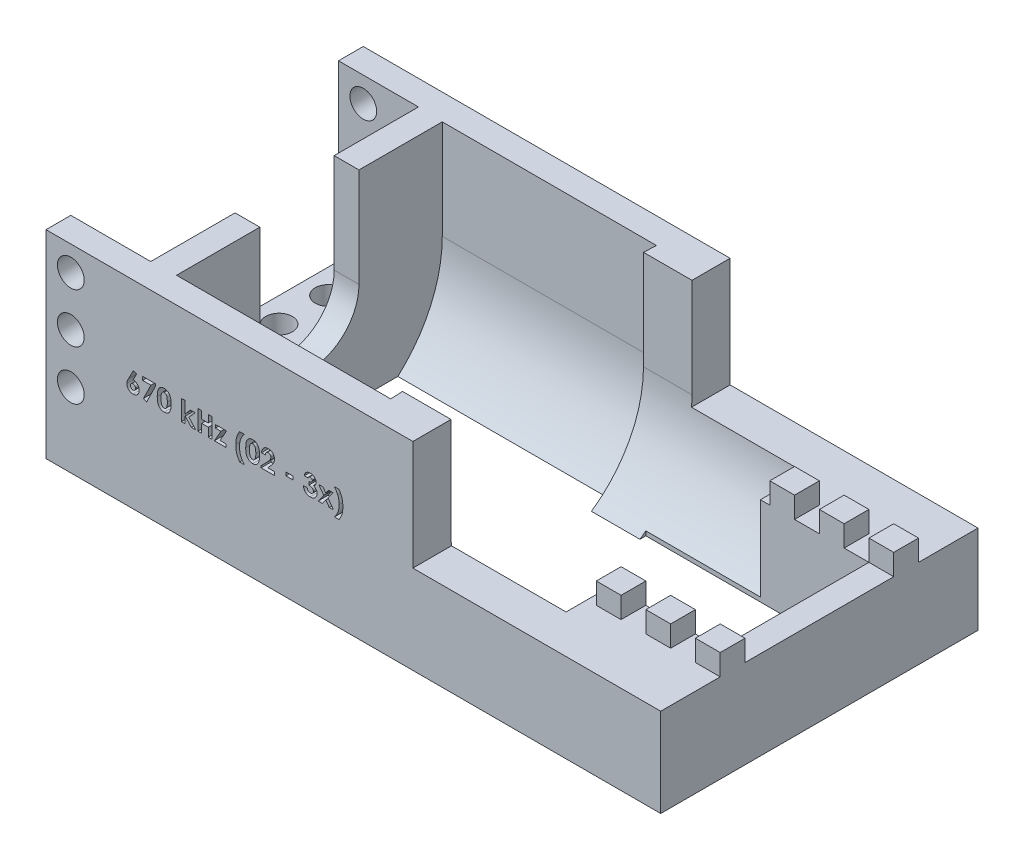
SolidWorks part; units mm, degrees
ref_plane "Front Plane" through (0, 0, 0) normal (0, 0, 1) x (1, 0, 0)
ref_plane "Top Plane" through (0, 0, 0) normal (0, 1, 0) x (1, 0, 0)
ref_plane "Right Plane" through (0, 0, 0) normal (1, 0, 0) x (0, 0, -1)
sketch "Sketch1" plane through (0, 0, 0) normal (0, 0, 1) x (1, 0, 0)
  line L1 (-76.2, -50.8) -> (81.28, -50.8)
  line L2 (-76.2, -50.8) -> (-76.2, 0)
  line L3 (-76.2, 0) -> (81.28, 0)
  line L4 (81.28, -50.8) -> (81.28, 0)
  line L5 (-76.2, -50.8) -> (81.28, 0) construction
  line L6 (-76.2, 0) -> (81.28, -50.8) construction
  point P0 (0, 0)
  dimension "D1" = 157.48
  dimension "D2" = 50.8
  dimension "D3" = 76.2
extrude "Boss-Extrude1" add sketch "Sketch1" along normal mid plane 81.28
sketch "Sketch2" plane through (0, 0, 0) normal (0, 0, 1) x (1, 0, 0)
  line L1 (-49.3609, 8.636) -> (-49.3609, -12.7)
  line L3 (81.28, 0) -> (-76.2, 0) construction
  line L4 (5.5031, 8.636) -> (5.3587, 5.4643)
  line L5 (3.9535, -25.4) -> (5.5031, 8.636) construction
  line L6 (-76.2, -25.4) -> (19.6294, -25.4)
  line L7 (19.6294, -25.4) -> (72.5335, -25.4)
  line L8 (-607.3619, -25.4) -> (19.6294, -25.4) construction
  line L9 (-49.3609, 8.636) -> (5.5031, 8.636)
  line L11 (5.3587, 5.4643) -> (47.1335, 5.4643)
  line L12 (47.1335, 5.4643) -> (47.1335, -15.494)
  line L13 (47.1335, -15.494) -> (72.5335, -15.494)
  line L14 (-49.3609, -12.7) -> (-76.2, -12.7)
  line L15 (-76.2, -12.7) -> (-76.2, -25.4)
  line L16 (81.28, 0) -> (-76.2, 0) construction
  line L17 (-76.2, 0) -> (-76.2, -50.8) construction
  line L20 (72.5335, -15.494) -> (72.5335, -25.4)
  line L21 (-76.2, 0) -> (-76.2, -50.8) construction
  point P23 (3.9535, -25.4)
  dimension "D1" = 25.4
  dimension "D2" = 54.864
  dimension "D3" = 34.036
  dimension "D4" = 68.58
  dimension "D5" = 9.906
  dimension "D6" = 3.175
  dimension "D7" = 26.8391
  dimension "D8" = 25.4
  dimension "D9" = 12.7
revolve "Cut-Revolve1" cut sketch "Sketch2" angle 360 about L8
sketch "Sketch37" plane through (81.28, 0, 0) normal (1, 0, 0) x (0, 0, -1)
  line L0 (40.64, -50.8) -> (40.64, 0) construction
  line L1 (-40.64, 0) -> (40.64, 0)
  line L2 (-40.64, 0) -> (-40.64, -25.4)
  line L3 (-40.64, -25.4) -> (40.64, -25.4)
  line L4 (40.64, 0) -> (40.64, -25.4)
  point P7 (0, -25.4)
  point P11 (0, 0)
  dimension "D1" = 25.4
extrude "Cut-Extrude32" cut sketch "Sketch37" against normal through all
sketch "Sketch39" plane through (0, -25.4, 0) normal (0, 1, 0) x (1, 0, 0)
  line L20 (-49.3609, -12.7) -> (-76.2, -12.7)
  line L21 (-49.3609, -12.7) -> (-76.2, -12.7)
  line L22 (-76.2, 40.64) -> (-76.2, 12.7)
  line L23 (-76.2, 40.64) -> (-76.2, 12.7)
  line L24 (-76.2, 12.7) -> (-49.3609, 12.7)
  line L25 (-76.2, -12.7) -> (-76.2, -40.64)
  line L26 (-76.2, -40.64) -> (81.28, -40.64)
  line L27 (81.28, -40.64) -> (81.28, 40.64)
  line L28 (81.28, 40.64) -> (-76.2, 40.64)
  line L29 (-76.2, 12.7) -> (-49.3609, 12.7)
  line L30 (-49.3609, 12.7) -> (-49.3609, 34.036)
  line L31 (-49.3609, 12.7) -> (-49.3609, 34.036)
  line L32 (-49.3609, 34.036) -> (5.5031, 34.036)
  line L33 (-49.3609, 34.036) -> (5.5031, 34.036)
  line L34 (5.5031, 34.036) -> (5.3587, 30.8643)
  line L35 (5.5031, 34.036) -> (5.3587, 30.8643)
  line L36 (5.3587, 30.8643) -> (47.1335, 30.8643)
  line L37 (5.3587, 30.8643) -> (47.1335, 30.8643)
  line L38 (47.1335, 30.8643) -> (47.1335, 9.906)
  line L39 (47.1335, 30.8643) -> (47.1335, 9.906)
  line L40 (47.1335, 9.906) -> (72.5335, 9.906)
  line L41 (47.1335, 9.906) -> (72.5335, 9.906)
  line L42 (72.5335, 9.906) -> (72.5335, -9.906)
  line L43 (72.5335, 9.906) -> (72.5335, -9.906)
  line L44 (72.5335, -9.906) -> (47.1335, -9.906)
  line L45 (72.5335, -9.906) -> (47.1335, -9.906)
  line L46 (47.1335, -9.906) -> (47.1335, -30.8643)
  line L47 (47.1335, -9.906) -> (47.1335, -30.8643)
  line L48 (47.1335, -30.8643) -> (5.3587, -30.8643)
  line L49 (-76.2, -12.7) -> (-76.2, -40.64)
  line L50 (-76.2, -40.64) -> (81.28, -40.64)
  line L51 (81.28, -40.64) -> (81.28, 40.64)
  line L52 (81.28, 40.64) -> (-76.2, 40.64)
  line L53 (47.1335, -30.8643) -> (5.3587, -30.8643)
  line L54 (5.3587, -30.8643) -> (5.5031, -34.036)
  line L55 (5.3587, -30.8643) -> (5.5031, -34.036)
  line L56 (5.5031, -34.036) -> (-49.3609, -34.036)
  line L57 (5.5031, -34.036) -> (-49.3609, -34.036)
  line L58 (-49.3609, -34.036) -> (-49.3609, -12.7)
  line L59 (-49.3609, -34.036) -> (-49.3609, -12.7)
  dimension "D1" = 0
extrude "Boss-Extrude5" add sketch "Sketch39" along normal blind 25.4
ref_axis "Axis1" through (72.5335, -25.4, 0) along (-1, 0, 0)
ref_plane "Plane_Mid" through (0, -25.4, 0) normal (0, 1, 0) x (1, 0, 0)
ref_plane "Plane3" through (0, -28.0987, 0) normal (0, 1, 0) x (1, 0, 0)
sketch "Sketch45" plane through (0, 0, 0) normal (0, 0, 1) x (1, 0, 0)
  line L1 (27.94, -28.0987) -> (-27.94, -28.0988) construction
  line L2 (81.28, 0) -> (17.78, 0)
  line L4 (81.28, 0) -> (81.28, -28.0987)
  line L5 (81.28, -28.0987) -> (17.78, -28.0987)
  line L8 (17.78, 0) -> (17.78, -28.0987)
  dimension "D1" = 63.5
extrude "Cut-Extrude54" cut sketch "Sketch45" against normal through all both and the other way through all
ref_plane "Plane1" through (-74.7609, 0, 0) normal (1, 0, 0) x (0, 0, -1)
sketch "Sketch97" plane through (0, 0, 0) normal (0, 1, 0) x (1, 0, 0)
  line L0 (-76.2, -40.64) -> (17.78, -40.64) construction
  line L1 (-76.2, 40.64) -> (-55.7109, 40.64)
  line L2 (-76.2, 40.64) -> (-76.2, -40.64)
  line L3 (-76.2, -40.64) -> (-55.7109, -40.64)
  line L4 (-55.7109, 40.64) -> (-55.7109, -40.64)
  line L5 (-49.3609, 12.7) -> (-49.3609, 34.036) construction
  dimension "D1" = 6.35
extrude "Cut-Extrude72" cut sketch "Sketch97" against normal offset from surface (44.45 mm away) 6.35 up to face at (2.54, -50.8, 0)
sketch "Sketch98" plane through (0, -44.45, 0) normal (0, 1, 0) x (1, 0, 0)
  line L0 (-76.2, -40.64) -> (-76.2, 40.64) construction
  circle A0 centre (-69.85, 25.4) radius 3.429
  circle A4 centre (-69.85, 12.7) radius 3.429
  circle A5 centre (-69.85, 0) radius 3.429
  circle A6 centre (-57.15, 25.4) radius 3.429 [skipped]
  circle A7 centre (-57.15, 12.7) radius 3.429 [skipped]
  circle A8 centre (-57.15, 0) radius 3.429 [skipped]
  circle A9 centre (-69.85, -12.7) radius 3.429
  circle A11 centre (-69.85, -25.4) radius 3.429
  circle A13 centre (-57.15, -12.7) radius 3.429 [skipped]
  circle A14 centre (-57.15, -25.4) radius 3.429 [skipped]
  dimension "D1" = 6.858
  dimension "D2" = 76.2
  dimension "D3" = 6.35
  dimension "D4" = 25.4
  dimension "D5" = 2
  dimension "D6" = 5
extrude "Cut-Extrude73" cut sketch "Sketch98" against normal through all
ref_plane "Plane2" through (0, -25.4, 0) normal (0, 1, 0) x (1, 0, 0)
ref_point "Point1"
sketch "Sketch99" plane through (0, 0, 0) normal (0, 1, 0) x (1, 0, 0)
  line L8 (81.28, 40.64) -> (81.28, -40.64) construction
  line L9 (17.78, 19.05) -> (74.93, 19.05)
  line L10 (17.78, 19.05) -> (17.78, -19.05)
  line L11 (17.78, -19.05) -> (74.93, -19.05)
  line L12 (74.93, 19.05) -> (74.93, -19.05)
  line L15 (17.78, 40.64) -> (17.78, 30.8643) construction
  point P7 (74.93, 0)
  dimension "D1" = 6.35
  dimension "D2" = 38.1
extrude "Cut-Extrude74" cut sketch "Sketch99" against normal through all
sketch "Sketch101" plane through (0, -28.0988, 0) normal (0, 1, 0) x (1, 0, 0)
  line L0 (49.53, 25.4) -> (55.88, 25.4)
  line L1 (49.53, 25.4) -> (49.53, 19.05)
  line L2 (49.53, 19.05) -> (55.88, 19.05)
  line L3 (55.88, 25.4) -> (55.88, 19.05)
  line L4 (62.23, 25.4) -> (68.58, 25.4)
  line L5 (62.23, 25.4) -> (62.23, 19.05)
  line L6 (62.23, 19.05) -> (68.58, 19.05)
  line L7 (68.58, 25.4) -> (68.58, 19.05)
  line L8 (74.93, 25.4) -> (81.28, 25.4)
  line L9 (74.93, 25.4) -> (74.93, 19.05)
  line L10 (74.93, 19.05) -> (81.28, 19.05)
  line L11 (81.28, 25.4) -> (81.28, 19.05)
  line L13 (81.28, 0) -> (0, 0) construction
  line L14 (81.28, 40.64) -> (81.28, -40.64) construction
  line L15 (81.28, -25.4) -> (81.28, -19.05)
  line L16 (74.93, -19.05) -> (81.28, -19.05)
  line L17 (74.93, -25.4) -> (74.93, -19.05)
  line L18 (74.93, -25.4) -> (81.28, -25.4)
  line L19 (68.58, -25.4) -> (68.58, -19.05)
  line L20 (62.23, -19.05) -> (68.58, -19.05)
  line L21 (62.23, -25.4) -> (62.23, -19.05)
  line L22 (62.23, -25.4) -> (68.58, -25.4)
  line L23 (55.88, -25.4) -> (55.88, -19.05)
  line L24 (49.53, -19.05) -> (55.88, -19.05)
  line L25 (49.53, -25.4) -> (49.53, -19.05)
  line L26 (49.53, -25.4) -> (55.88, -25.4)
  point P31 (74.93, 22.225)
  dimension "D1" = 6.35
  dimension "D2" = 6.35
  dimension "D3" = 6.35
extrude "Boss-Extrude7" add sketch "Sketch101" along normal blind 5.3975
sketch "Sketch102" plane through (0, 0, 0) normal (0, 1, 0) x (1, 0, 0)
  line L0 (-76.2, -40.64) -> (-76.2, 40.64) construction
  line L1 (-55.7109, 40.64) -> (-76.2, 40.64)
  line L2 (-55.7109, 40.64) -> (-55.7109, 34.29)
  line L3 (-55.7109, 34.29) -> (-76.2, 34.29)
  line L4 (-76.2, 40.64) -> (-76.2, 34.29)
  line L5 (-55.7109, -40.64) -> (-76.2, -40.64)
  line L6 (-55.7109, -40.64) -> (-55.7109, -34.29)
  line L7 (-55.7109, -34.29) -> (-76.2, -34.29)
  line L8 (-76.2, -40.64) -> (-76.2, -34.29)
  dimension "D1" = 6.35
extrude "Boss-Extrude8" add sketch "Sketch102" against normal up to next
sketch "Sketch103" plane through (0, 0, 40.64) normal (0, 0, 1) x (1, 0, 0)
  line L0 (-76.2, 0) -> (-76.2, -50.8) construction
  line L1 (-76.2, 0) -> (17.78, 0) construction
  circle A0 centre (-69.85, -6.35) radius 3.429
  circle A1 centre (-69.85, -19.05) radius 3.429
  circle A2 centre (-69.85, -31.75) radius 3.429
  circle A4 centre (-69.85, -44.45) radius 3.429 [skipped]
  dimension "D1" = 6.858
  dimension "D2" = 6.35
  dimension "D3" = 6.35
  dimension "D4" = 4
extrude "Cut-Extrude75" cut sketch "Sketch103" against normal through all
sketch "Sketch104" plane through (0, 0, 40.64) normal (0, 0, 1) x (1, 0, 0)
  line L0 (-76.2, 0) -> (-76.2, -50.8) construction
  line L1 (-76.2, -25.1545) -> (17.78, -25.4) construction
  text T0 "<b>670 kHz (02 - 3x)</b>" font "Century Gothic" height 5.08
  point P0 (0, 0)
  point P2 (0, 0)
extrude "Cut-Extrude76" cut sketch "Sketch104" against normal blind 2.54
